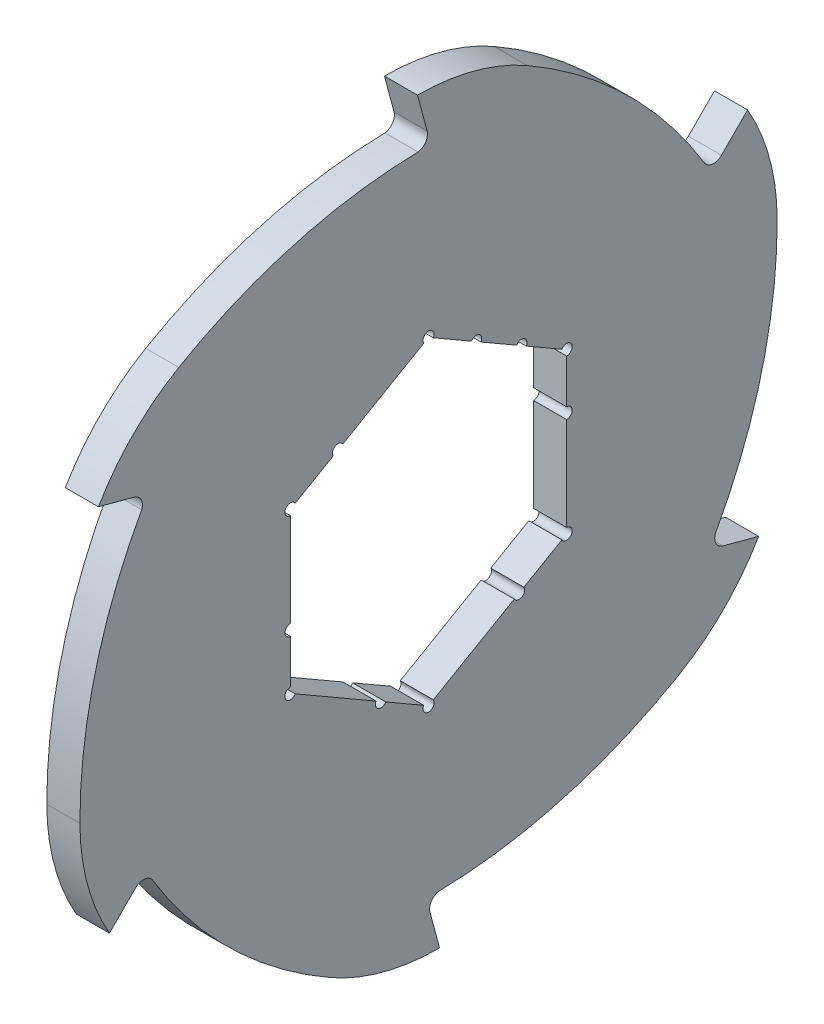
SolidWorks part; units mm, degrees
note: '?' marks a value the reader was unsure of.
material "1.0037 (S235JR)"
ref_plane "Alzado" through (0, 0, 0) normal (0, 0, 1) x (1, 0, 0)
ref_plane "Planta" through (0, 0, 0) normal (0, 1, 0) x (1, 0, 0)
ref_plane "Vista lateral" through (0, 0, 0) normal (1, 0, 0) x (0, 0, -1)
sketch "Sketch1" plane through (0, 0, 0) normal (1, 0, 0) x (0, 0, -1)
  line L0 (-56.6126, 0) -> (65.57, 0) construction
  line L1 (25.05, 14.4626) -> (0, 28.9252)
  line L2 (0, 28.9252) -> (-25.05, 14.4626)
  line L3 (-25.05, 14.4626) -> (-25.05, -14.4626)
  line L4 (-25.05, -14.4626) -> (0, -28.9252)
  line L5 (0, -28.9252) -> (25.05, -14.4626)
  line L6 (25.05, -14.4626) -> (25.05, 14.4626)
  circle A0 centre (0, 0) radius 25.05 construction
  circle A1 centre (0, 0) radius 59
  dimension "D2" = 118
  dimension "D1" = 50.1
  dimension "D3" = 30
extrude "Extrude1" add sketch "Sketch1" along normal mid plane 6
ref_axis "Axis1" through (-5.5, 0, 0) along (1, 0, 0)?
sketch "Sketch2" plane through (0, 0, 0) normal (1, 0, 0) x (0, 0, -1)
  line L0 (-2, 67.9618) -> (-0.2627, 61.4781)
  line L1 (0, 0) -> (0, 77.6328) construction
  line L4 (-2.1226, 58.9618) -> (0, 0) construction
  circle A0 centre (0, 0) radius 59 construction
  arc A1 (-2, 67.9618) -> (17.9271, 62.6448) centre (-2, 27.9618) cw
  arc A3 (51.2137, 29.2943) -> (-2.1226, 58.9618) centre (0, 0) ccw
  arc A4 (-0.2627, 61.4781) -> (-2.1226, 58.9618) centre (-2.1946, 60.9605) cw
  arc A5 (17.9271, 62.6448) -> (51.2137, 29.2943) centre (-26.9089, -15.3919) cw
  point P10 (-2, 67.9618)
  dimension "D2" = 40
  dimension "D4" = 2
  dimension "D3" = 9
  dimension "D6" = 90
  dimension "D1" = 15
  dimension "D5" = 2
extrude "Extrude2" add sketch "Sketch2" against normal mid plane 6
fillet "Fillet1" [suppressed] radius 0.6
pattern_circular "CirPattern1" count 6 over 360 about axis through (0, 0, 0) along (1, 0, 0) of "Extrude2", "Fillet1"
sketch "Sketch4" [suppressed] plane through (3, 0, 0) normal (1, 0, 0) x (0, 0, -1)
  circle A0 centre (0, 0) radius 67.9646 construction
  dimension "D1" = 135.9291
hole_wizard "Ø2.0 (2) Diameter Hole1" positions "Sketch5" profile "Sketch7" hole size "Ø2.0" standard "ISO" end condition up to next
sketch "Sketch5" plane through (3, 0, 0) normal (1, 0, 0) x (0, 0, -1)
  point P0 (0, 28.9252)
  point P7 (25.05, 14.4626)
  point P8 (25.05, -14.4626)
  point P9 (0, -28.9252)
  point P10 (-25.05, -14.4626)
  point P11 (-25.05, 14.4626)
  dimension "D1" = 6
sketch "Sketch7" plane through (3, 28.9252, 0) normal (0, 1, 0) x (0, 0, -1)
  line L0 (0, 0) -> (0, 6)
  line L1 (0, 6) -> (1, 6)
  line L2 (1, 6) -> (1, 0)
  line L5 (1, 0) -> (0, 0)
  line L11 (0, -6.35) -> (0, 107.95) construction
  dimension "Diámetro de taladro hasta el siguiente" = 2
  dimension "Profundidad de taladro hasta el siguiente" = 6
hole_wizard "Ø2.0 (2) Diameter Hole3" positions "Sketch10" profile "Sketch11" hole size "Ø2.0" standard "ISO" end condition up to next
sketch "Sketch10" plane through (3, 0, 0) normal (1, 0, 0) x (0, 0, -1)
  line L0 (0.866, 28.4252) -> (8.6387, 23.9377) construction
  line L1 (24.184, 14.9626) -> (0.866, 28.4252) construction
  line L2 (8.6387, 23.9377) -> (16.4113, 19.4502) construction
  line L3 (16.4113, 19.4502) -> (24.184, 14.9626) construction
  point P2 (8.6387, 23.9377)
sketch "Sketch11" plane through (3, 23.9377, -8.6387) normal (0, 1, 0) x (0, 0, -1)
  line L0 (0, 0) -> (0, 6.001)
  line L1 (0, 6.001) -> (1, 6.001)
  line L2 (1, 6.001) -> (1, 0)
  line L5 (1, 0) -> (0, 0)
  line L11 (0, -6.35) -> (0, 107.95) construction
  dimension "Diámetro de taladro hasta el siguiente" = 2
  dimension "Profundidad de taladro hasta el siguiente" = 6.001
hole_wizard "Ø2.0 (2) Diameter Hole4" positions "Sketch12" profile "Sketch13" hole size "Ø2.0" standard "ISO" end condition up to next
sketch "Sketch12" plane through (3, 0, 0) normal (1, 0, 0) x (0, 0, -1)
  line L0 (24.184, 14.9626) -> (9.5047, 23.4377) construction
  point P0 (16.8443, 19.2002)
sketch "Sketch13" plane through (3, 19.2002, -16.8443) normal (0, 1, 0) x (0, 0, -1)
  line L0 (0, 0) -> (0, 6)
  line L1 (0, 6) -> (1, 6)
  line L2 (1, 6) -> (1, 0)
  line L5 (1, 0) -> (0, 0)
  line L11 (0, -6.35) -> (0, 107.95) construction
  dimension "Diámetro de taladro hasta el siguiente" = 2
  dimension "Profundidad de taladro hasta el siguiente" = 6
pattern_circular "CirPattern2" count 6 every 60 about axis through (0, 0, 0) along (1, 0, 0) of "Ø2.0 (2) Diameter Hole3"
pattern_circular "CirPattern3" [suppressed] count 1 every? 60? about axis through (-5.5, 0, 0) along (1, 0, 0)
equation "\"D1@Extrude2\"=\"D1@Extrude1\""
